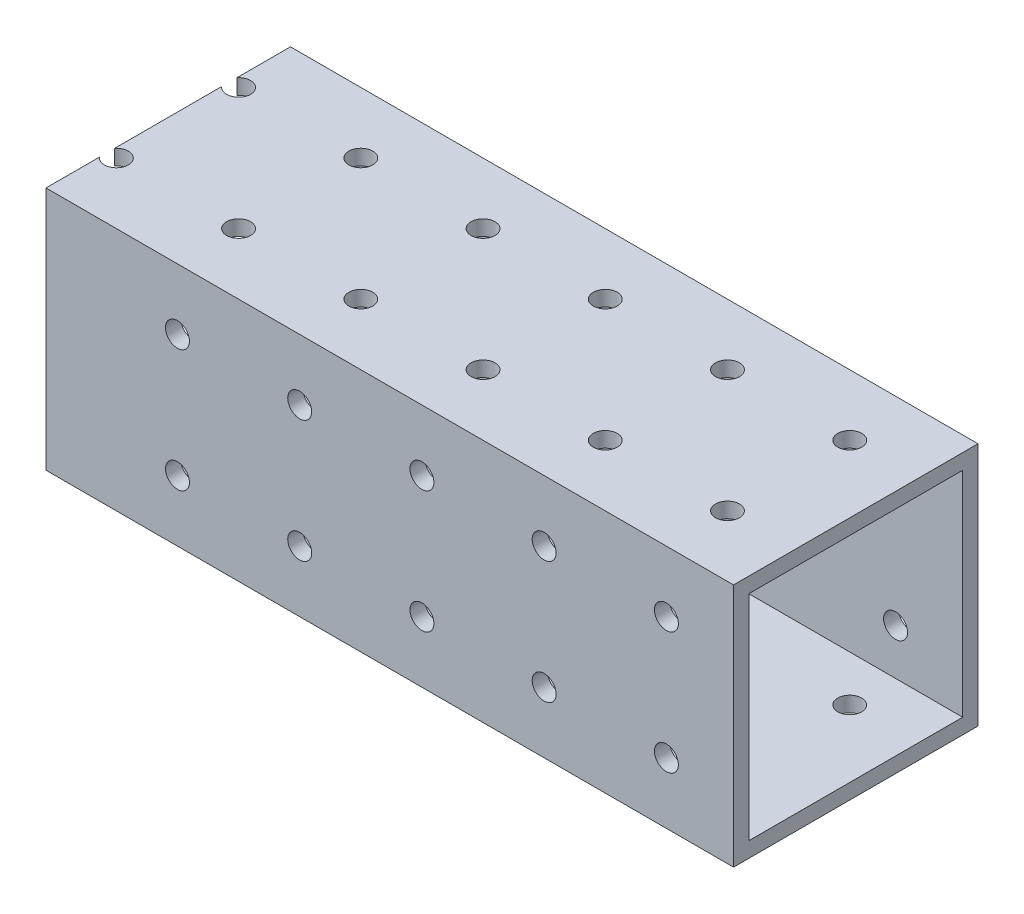
SolidWorks part; units mm, degrees
material "6061-T6 (SS)"
ref_plane "Front Plane" through (0, 0, 0) normal (0, 0, 1) x (1, 0, 0)
ref_plane "Top Plane" through (0, 0, 0) normal (0, 1, 0) x (1, 0, 0)
ref_plane "Right Plane" through (0, 0, 0) normal (1, 0, 0) x (0, 0, -1)
sketch "Sketch1" plane through (0, 0, 0) normal (1, 0, 0) x (0, 0, -1)
  line L1 (0, 0) -> (50.8, 0)
  line L2 (0, 0) -> (0, 50.8)
  line L3 (0, 50.8) -> (50.8, 50.8)
  line L4 (50.8, 0) -> (50.8, 50.8)
  dimension "D1" = 50.8
extrude "Boss-Extrude1" add sketch "Sketch1" along normal blind 142.875
shell "Shell1" thickness 3.175 removed face at (0, 25.4, -25.4) removed face at (142.875, 25.4, -25.4)
sketch "Sketch2" plane through (0, 0, -50.8) normal (0, 0, -1) x (-1, 0, 0)
  circle A0 centre (-128.9208, 38.1) radius 2.4892 construction
  circle A1 centre (-103.5208, 38.1) radius 2.4892 construction
  circle A2 centre (-78.1208, 38.1) radius 2.4892 construction
  circle A3 centre (-52.7208, 38.1) radius 2.4892 construction
  circle A4 centre (-27.3208, 38.1) radius 2.4892 construction
  circle A5 centre (-27.3208, 12.7) radius 2.4892 construction
  circle A6 centre (-52.7208, 12.7) radius 2.4892 construction
  circle A7 centre (-78.1208, 12.7) radius 2.4892 construction
  circle A8 centre (-103.5208, 12.7) radius 2.4892 construction
  circle A9 centre (-128.9208, 12.7) radius 2.4892 construction
  circle A10 centre (-128.9208, 38.1) radius 2.4892
  circle A11 centre (-103.5208, 38.1) radius 2.4892
  circle A12 centre (-78.1208, 38.1) radius 2.4892
  circle A13 centre (-52.7208, 38.1) radius 2.4892
  circle A14 centre (-27.3208, 38.1) radius 2.4892
  circle A15 centre (-27.3208, 12.7) radius 2.4892
  circle A16 centre (-52.7208, 12.7) radius 2.4892
  circle A17 centre (-78.1208, 12.7) radius 2.4892
  circle A18 centre (-103.5208, 12.7) radius 2.4892
  circle A19 centre (-128.9208, 12.7) radius 2.4892
extrude "Cut-Extrude1" cut sketch "Sketch2" against normal through all
sketch "Sketch3" plane through (0, 0, 0) normal (0, -1, 0) x (1, 0, 0)
  line L1 (128.9208, -38.1) -> (128.9208, -12.7) construction
  line L2 (128.9208, -12.7) -> (128.9208, 12.7) construction
  line L3 (287.6708, 0) -> (-309.2292, 0) construction
  line L4 (142.875, -50.8) -> (0, -50.8) construction
  circle A0 centre (128.9208, -12.7) radius 2.4892
  circle A1 centre (128.9208, -38.1) radius 2.4892
  point P10 (0, 0)
  point P11 (128.9208, 12.7)
  dimension "D1" = 4.9784
  dimension "D2" = 12.7
  dimension "D3" = 12.7
extrude "Cut-Extrude2" cut sketch "Sketch3" against normal through all
pattern_linear "LPattern1" count 6 spacing 25.4 along (-1, 0, 0) of "Cut-Extrude2"
